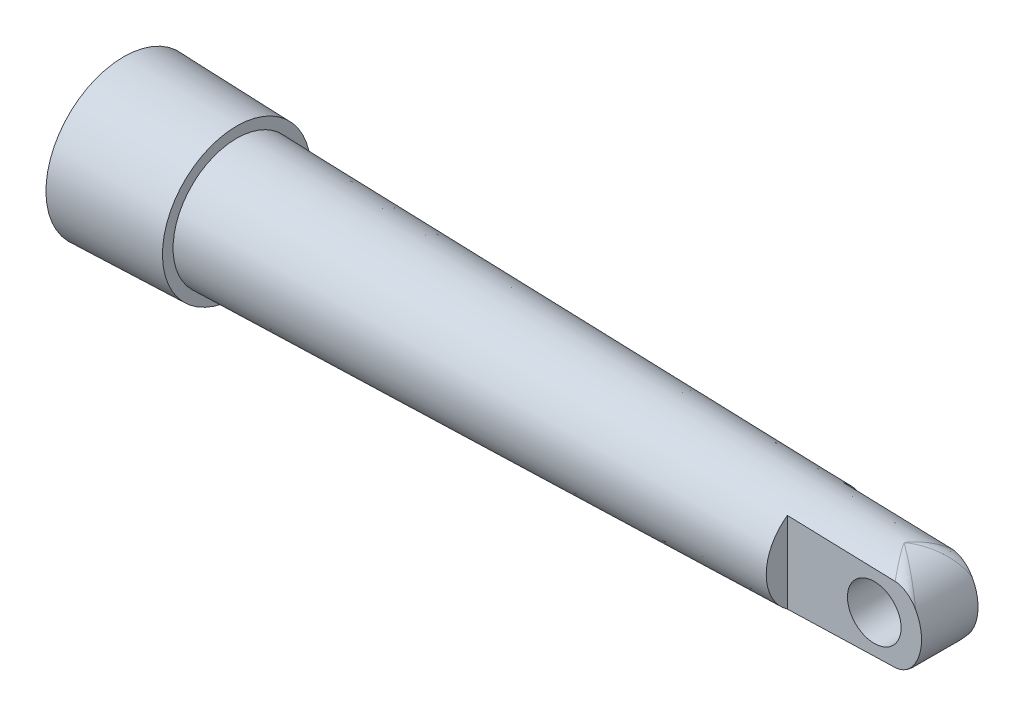
SolidWorks part; units mm, degrees
ref_plane "Front Plane" through (0, 0, 0) normal (0, 0, 1) x (1, 0, 0)
ref_plane "Top Plane" through (0, 0, 0) normal (0, 1, 0) x (1, 0, 0)
ref_plane "Right Plane" through (0, 0, 0) normal (1, 0, 0) x (0, 0, -1)
sketch "Sketch1" plane through (0, 0, 0) normal (0, 0, 1) x (1, 0, 0)
  line L0 (0, 0) -> (0, 2.75)
  line L1 (0, 2.75) -> (4, 2.625)
  line L2 (4, 2.625) -> (4, 2.25)
  line L3 (4, 2.25) -> (24.5, 1.75)
  line L4 (24.5, 1.75) -> (24.5, 0)
  line L5 (24.5, 0) -> (0, 0)
  dimension "D1" = 2.75
  dimension "D2" = 2.625
  dimension "D3" = 1.75
  dimension "D4" = 2.25
  dimension "D5" = 24.5
  dimension "D6" = 4
revolve "Revolve1" add sketch "Sketch1" angle 360 about L5
sketch "Sketch2" plane through (0, 0, 0) normal (0, 0, 1) x (1, 0, 0)
  line L0 (24.5, 0) -> (31.6718, 0) construction
  line L1 (24.5, -1.75) -> (24.5, 1.75) construction
  line L2 (24.5, 1.75) -> (27.575, 1.675)
  line L3 (27.575, -1.675) -> (24.5, -1.75)
  line L4 (24.5, 1.75) -> (4, 2.25) construction
  line L5 (4, -2.25) -> (24.5, -1.75) construction
  line L6 (24.5, 1.75) -> (24.5, -1.75)
  arc A0 (27.575, 1.675) -> (27.575, -1.675) centre (27.575, 0) cw
  point P8 (27.575, 0)
  dimension "D1" = 4.75
extrude "Boss-Extrude1" add sketch "Sketch2" along normal mid plane 2
sketch "Sketch4" plane through (0, 0, 0) normal (0, 0, 1) x (1, 0, 0)
  line L0 (24.5, 1.75) -> (24.5, 2.5)
  line L1 (24.5, 2.5) -> (31.3804, 2.5)
  line L2 (31.3804, 2.5) -> (31.3861, 1.582)
  line L3 (31.3861, 1.582) -> (24.5, 1.75)
  line L4 (27.575, 1.675) -> (24.5, 1.75) construction
  line L5 (24.5, 0) -> (31.7503, 0) construction
  line L6 (24.5, 1.4361) -> (24.5, -1.4361) construction
  dimension "D1" = 2.5
revolve "Cut-Revolve1" cut sketch "Sketch4" angle 360 about L5
sketch "Sketch5" plane through (0, 0, 1) normal (0, 0, 1) x (1, 0, 0)
  circle A0 centre (27.575, 0) radius 0.95
  dimension "D1" = 1.9
extrude "Cut-Extrude1" cut sketch "Sketch5" against normal through all
fillet "Fillet1" radius 0.5 2 edges at (27.6575, -1.673, -0.0084) (27.6575, 1.673, 0.0084)
sketch "Sketch6" plane through (0, 0, 0) normal (-1, 0, 0) x (0, 0, 1)
  circle A0 centre (0, 0) radius 1
  dimension "D1" = 2
extrude "Cut-Extrude2" cut sketch "Sketch6" against normal blind 15
